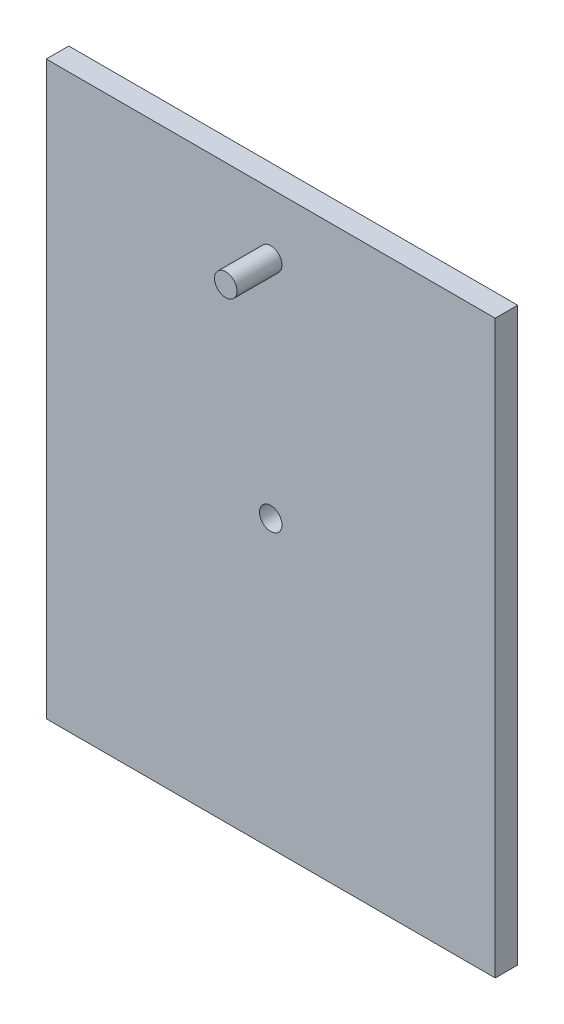
SolidWorks part; units mm, degrees
ref_plane "Front Plane" through (0, 0, 0) normal (0, 0, 1) x (1, 0, 0)
ref_plane "Top Plane" through (0, 0, 0) normal (0, 1, 0) x (1, 0, 0)
ref_plane "Right Plane" through (0, 0, 0) normal (1, 0, 0) x (0, 0, -1)
sketch "Sketch1" plane through (0, 0, 0) normal (0, 0, 1) x (1, 0, 0)
  line L0 (-199.5719, 0) -> (199.5719, 0) construction
  line L1 (-199.5719, 254) -> (199.5719, 254)
  line L2 (-199.5719, 254) -> (-199.5719, -254)
  line L3 (-199.5719, -254) -> (199.5719, -254)
  line L4 (199.5719, 254) -> (199.5719, -254)
  line L5 (-199.5719, 254) -> (199.5719, -254) construction
  line L6 (-199.5719, -254) -> (199.5719, 254) construction
  line L7 (0, 254) -> (0, -254) construction
  circle A0 centre (0, 0) radius 10
  circle A1 centre (0, 200) radius 10
  point P0 (0, 0)
  dimension "D1" = 20
extrude "Boss-Extrude1" add sketch "Sketch1" along normal blind 20
extrude "Boss-Extrude2" add sketch "Sketch1<2>" along normal blind 60 contours A1
sketch "Sketch1<2>" plane through (0, 0, 0) normal (0, 0, 1) x (1, 0, 0) same geometry as "Sketch1"
